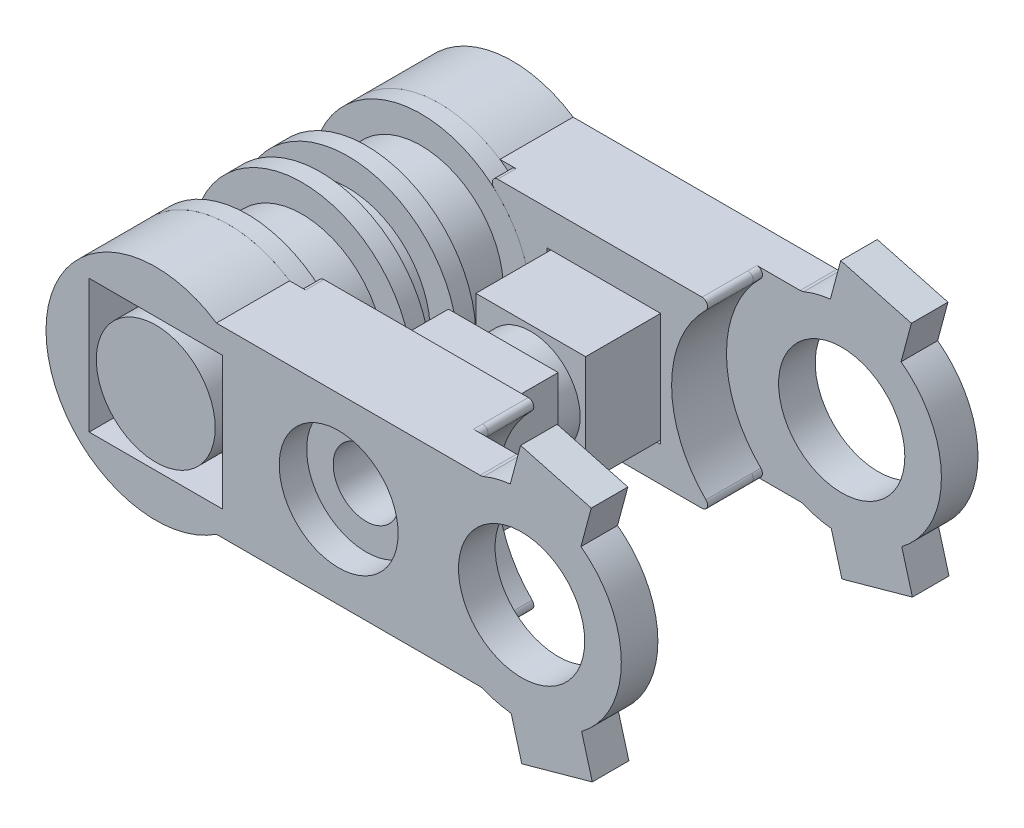
SolidWorks part; units mm, degrees
material "ABS"
ref_plane "正面" through (0, 0, 0) normal (0, 0, 1) x (1, 0, 0)
ref_plane "平面" through (0, 0, 0) normal (0, 1, 0) x (1, 0, 0)
ref_plane "右側面" through (0, 0, 0) normal (1, 0, 0) x (0, 0, -1)
sketch "ｽｹｯﾁ1" plane through (0, 0, 0) normal (0, 0, 1) x (1, 0, 0)
  circle A0 centre (0, 0) radius 4.5
  dimension "D1" = 9
extrude "ﾎﾞｽ - 押し出し1" add sketch "ｽｹｯﾁ1" along normal blind 3
sketch "ｽｹｯﾁ2" plane through (0, 0, 0) normal (0, 0, -1) x (-1, 0, 0)
  circle A0 centre (0, 0) radius 6
  dimension "D1" = 12
extrude "ﾎﾞｽ - 押し出し2" add sketch "ｽｹｯﾁ2" along normal blind 1
sketch "ｽｹｯﾁ3" plane through (0, 0, -1) normal (0, 0, -1) x (-1, 0, 0)
  circle A0 centre (0, 0) radius 4.5 construction
  circle A1 centre (0, 0) radius 4.5
extrude "ﾎﾞｽ - 押し出し3" add sketch "ｽｹｯﾁ3" along normal blind 1.5
sketch "ｽｹｯﾁ4" plane through (0, 0, -2.5) normal (0, 0, -1) x (-1, 0, 0)
  circle A1 centre (0, 0) radius 6
  circle A2 centre (0, 0) radius 6
  dimension "D1" = 0
extrude "ﾎﾞｽ - 押し出し4" add sketch "ｽｹｯﾁ4" along normal blind 1
sketch "ｽｹｯﾁ5" plane through (0, 0, -3.5) normal (0, 0, -1) x (-1, 0, 0)
  circle A0 centre (0, 0) radius 4.5 construction
  circle A1 centre (0, 0) radius 4.5
extrude "ﾎﾞｽ - 押し出し5" add sketch "ｽｹｯﾁ5" along normal blind 3
sketch "ｽｹｯﾁ6" plane through (0, 0, -6.5) normal (0, 0, -1) x (-1, 0, 0)
  circle A1 centre (0, 0) radius 6
  circle A2 centre (0, 0) radius 6
  dimension "D1" = 0
extrude "ﾎﾞｽ - 押し出し6" add sketch "ｽｹｯﾁ6" along normal blind 1
sketch "ｽｹｯﾁ7" plane through (0, 0, 3) normal (0, 0, 1) x (1, 0, 0)
  circle A1 centre (0, 0) radius 6
  circle A2 centre (0, 0) radius 6
  dimension "D1" = 0
extrude "ﾎﾞｽ - 押し出し7" add sketch "ｽｹｯﾁ7" along normal blind 1
sketch "ｽｹｯﾁ10" plane through (0, 0, 4) normal (0, 0, 1) x (1, 0, 0)
  line L1 (3.5, -3.5) -> (-3.5, -3.5)
  line L2 (3.5, -3.5) -> (3.5, 3.5)
  line L3 (3.5, 3.5) -> (-3.5, 3.5)
  line L4 (-3.5, -3.5) -> (-3.5, 3.5)
  line L5 (3.5, -3.5) -> (-3.5, 3.5) construction
  line L6 (3.5, 3.5) -> (-3.5, -3.5) construction
  point P0 (0, 0)
  dimension "D1" = 7
  dimension "D2" = 7
extrude "ﾎﾞｽ - 押し出し10" add sketch "ｽｹｯﾁ10" along normal blind 1.5
sketch "ｽｹｯﾁ11" plane through (0, 0, 5.5) normal (0, 0, 1) x (1, 0, 0)
  circle A0 centre (0, 0) radius 3.25
  dimension "D1" = 6.5
extrude "ﾎﾞｽ - 押し出し11" add sketch "ｽｹｯﾁ11" along normal blind 2.5
ref_plane "平面1" through (0, 0, -1.75) normal (0, 0, 1) x (1, 0, 0)
mirror "ﾐﾗｰ1" about plane through (0, 0, -1.75) normal (0, 0, 1) of "ﾎﾞｽ - 押し出し11", "ﾎﾞｽ - 押し出し10"
sketch "ｽｹｯﾁ12" plane through (0, 0, 4) normal (0, 0, 1) x (1, 0, 0)
  line L0 (0, 0) -> (20, 0) construction
  line L1 (3.3166, 5) -> (16.1672, 5)
  line L3 (16.1672, -5) -> (3.3166, -5)
  line L8 (3.64, -3.64) -> (3.64, 3.64)
  line L9 (-3.64, -3.64) -> (3.64, -3.64)
  line L10 (-3.64, 3.64) -> (-3.64, -3.64)
  line L11 (3.64, 3.64) -> (-3.64, 3.64)
  line L12 (3.64, -3.64) -> (3.64, 3.64)
  line L13 (-3.64, -3.64) -> (3.64, -3.64)
  line L14 (-3.64, 3.64) -> (-3.64, -3.64)
  line L15 (3.64, 3.64) -> (-3.64, 3.64)
  circle A0 centre (0, 0) radius 6 construction
  circle A1 centre (20, 0) radius 3.45 construction
  arc A2 (3.3166, 5) -> (3.3166, -5) centre (0, 0) ccw
  circle A3 centre (20, 0) radius 5.45 construction
  circle A4 centre (20, 0) radius 6.3 construction
  arc A5 (16.1672, 5) -> (16.1672, -5) centre (20, 0) ccw
  circle A6 centre (20, 0) radius 6 construction
  circle A7 centre (0, 0) radius 6 construction
  circle A8 centre (20, 0) radius 3.25 construction
  circle A9 centre (0, 0) radius 3.25 construction
  dimension "D3" = 20
  dimension "D6" = 0.3
  dimension "D2" = 5
  dimension "D7" = 5
  dimension "D4" = 0.2
  dimension "D5" = 2
  dimension "D1" = 0.14
extrude "ﾎﾞｽ - 押し出し12" add sketch "ｽｹｯﾁ12" along normal blind 1.5 separate body
sketch "ｽｹｯﾁ13" plane through (0, 0, 5.5) normal (0, 0, 1) x (1, 0, 0)
  line L6 (16.1672, 5) -> (3.3166, 5) construction
  line L9 (16.1672, 5) -> (3.3166, 5) construction
  line L10 (15.3664, 5) -> (3.7135, 5)
  line L11 (15.3664, -5) -> (3.7135, -5)
  circle A1 centre (0, 0) radius 3.25 construction
  arc A7 (16.1672, 5) -> (16.1672, -5) centre (20, 0) ccw construction
  arc A8 (15.577, 4.4864) -> (15.577, -4.4864) centre (20, 0) ccw
  circle A10 centre (0, 0) radius 5.69 construction
  circle A11 centre (0, 0) radius 3.39 construction
  circle A12 centre (0, 0) radius 5.39 construction
  arc A13 (3.5275, 4.4646) -> (3.5275, -4.4646) centre (0, 0) cw
  arc A14 (15.3664, -5) -> (15.577, -4.4864) centre (15.3664, -4.7) ccw
  arc A15 (15.577, 4.4864) -> (15.3664, 5) centre (15.3664, 4.7) ccw
  arc A16 (3.7135, 5) -> (3.5275, 4.4646) centre (3.7135, 4.7) ccw
  arc A17 (3.5275, -4.4646) -> (3.7135, -5) centre (3.7135, -4.7) ccw
  point P24 (2.7159, 5)
  point P29 (2.7159, -5)
  dimension "D1" = 0.14
  dimension "D3" = 0.3
  dimension "D4" = 2
  dimension "D2" = 0.3
extrude "ﾎﾞｽ - 押し出し13" add sketch "ｽｹｯﾁ13" along normal blind 0.5
fillet "ﾌｨﾚｯﾄ9" radius 0.3 2 edges at (16.1672, -5, 4.75) (16.1672, 5, 4.75)
sketch "ｽｹｯﾁ14" plane through (0, 0, 6) normal (0, 0, 1) x (1, 0, 0)
  line L0 (3.7135, 5) -> (17.7301, 5)
  line L3 (3.7135, -5) -> (17.7301, -5)
  arc A0 (17.7301, 5) -> (17.9208, 5.0378) centre (17.7301, 5.5) ccw
  arc A1 (17.7301, -5) -> (17.9208, -5.0378) centre (17.7301, -5.5) cw
  arc A4 (3.5275, -4.4646) -> (3.7135, -5) centre (3.7135, -4.7) ccw construction
  arc A7 (3.5275, -4.4646) -> (3.5275, 4.4646) centre (0, 0) ccw construction
  arc A8 (3.7135, 5) -> (3.5275, 4.4646) centre (3.7135, 4.7) ccw construction
  arc A9 (3.5275, -4.4646) -> (3.7135, -5) centre (3.7135, -4.7) ccw
  arc A10 (3.7135, 5) -> (3.5275, 4.4646) centre (3.7135, 4.7) ccw
  arc A11 (3.5275, -4.4646) -> (3.5275, 4.4646) centre (0, 0) ccw
  circle A12 centre (20, 0) radius 5.45 construction
  arc A13 (17.9208, 5.0378) -> (17.9208, -5.0378) centre (20, 0) cw
  circle A14 centre (20, 0) radius 3.45 construction
  circle A15 centre (20, 0) radius 3.45
  point P19 (17.8315, -5)
  point P22 (17.8315, 5)
  point P24 (17.8315, 5)
  point P27 (17.8315, -5)
  dimension "D1" = 0.5
extrude "ﾎﾞｽ - 押し出し14" add sketch "ｽｹｯﾁ14" along normal blind 2
sketch "ｽｹｯﾁ15" plane through (0, 0, 4) normal (0, 0, -1) x (-1, 0, 0)
  line L0 (-15.3664, 5) -> (-4.1952, 5)
  line L1 (-3.3166, 5) -> (-16.1672, 5) construction
  line L2 (-15.3664, -5) -> (-4.1952, -5)
  line L3 (-16.1672, -5) -> (-3.3166, -5) construction
  circle A2 centre (0, 0) radius 6 construction
  arc A3 (-3.9955, 4.4762) -> (-3.9955, -4.4762) centre (0, 0) ccw
  arc A7 (-4.1952, -5) -> (-3.9955, -4.4762) centre (-4.1952, -4.7) ccw
  arc A8 (-4.1952, 5) -> (-3.9955, 4.4762) centre (-4.1952, 4.7) cw
  arc A10 (-15.577, -4.4864) -> (-15.3664, -5) centre (-15.3664, -4.7) ccw construction
  arc A11 (-15.577, -4.4864) -> (-15.577, 4.4864) centre (-20, 0) ccw construction
  arc A12 (-15.3664, 5) -> (-15.577, 4.4864) centre (-15.3664, 4.7) ccw construction
  arc A13 (-15.577, -4.4864) -> (-15.3664, -5) centre (-15.3664, -4.7) ccw
  arc A14 (-15.577, -4.4864) -> (-15.577, 4.4864) centre (-20, 0) ccw
  arc A15 (-15.3664, 5) -> (-15.577, 4.4864) centre (-15.3664, 4.7) ccw
  point P26 (-3.3166, -5)
  point P29 (-3.3166, 5)
  dimension "D2" = 0.3
extrude "ﾎﾞｽ - 押し出し15" add sketch "ｽｹｯﾁ15" along normal blind 1
mirror "ﾐﾗｰ2" about plane through (0, 0, -1.75) normal (0, 0, 1) of bodies 116
sketch "ｽｹｯﾁ16" plane through (0, 0, 8) normal (0, 0, 1) x (1, 0, 0)
  line L0 (0, 0) -> (20, 0) construction
  circle A0 centre (20, 0) radius 3.45 construction
  circle A1 centre (10, 0) radius 1.8
  dimension "D1" = 3.6
extrude "ｶｯﾄ - 押し出し1" cut sketch "ｽｹｯﾁ16" against normal through all
sketch "ｽｹｯﾁ17" plane through (0, 0, -6.5) normal (0, 0, 1) x (1, 0, 0)
  line L1 (13.1, -3.1) -> (6.9, -3.1)
  line L2 (13.1, -3.1) -> (13.1, 3.1)
  line L3 (13.1, 3.1) -> (6.9, 3.1)
  line L4 (6.9, -3.1) -> (6.9, 3.1)
  line L5 (13.1, -3.1) -> (6.9, 3.1) construction
  line L6 (13.1, 3.1) -> (6.9, -3.1) construction
  point P0 (10, 0)
  dimension "D2" = 6.2
  dimension "D1" = 6.2
extrude "ｶｯﾄ - 押し出し2" cut sketch "ｽｹｯﾁ17" against normal blind 2
sketch "ｽｹｯﾁ18" plane through (0, 0, 3) normal (0, 0, -1) x (-1, 0, 0)
  line L0 (-7, 3) -> (-13, 3)
  line L5 (-13, 3) -> (-13, -3)
  line L6 (-13, -3) -> (-7, -3)
  line L7 (-7, -3) -> (-7, 3)
  line L8 (-13.1, -3.1) -> (-6.9, -3.1)
  line L9 (-6.9, -3.1) -> (-6.9, 3.1)
  line L10 (-6.9, 3.1) -> (-13.1, 3.1)
  line L11 (-13.1, 3.1) -> (-13.1, -3.1)
  line L12 (-13.1, -3.1) -> (-6.9, -3.1) construction
  line L13 (-6.9, -3.1) -> (-6.9, 3.1) construction
  line L14 (-6.9, 3.1) -> (-13.1, 3.1) construction
  line L15 (-13.1, 3.1) -> (-13.1, -3.1) construction
  dimension "D1" = 0
  dimension "D2" = 0.1
extrude "ﾎﾞｽ - 押し出し16" add sketch "ｽｹｯﾁ18" along normal up to surface (11.5 mm away) up to face at (10, 0, -8.5)
sketch "ｽｹｯﾁ19" plane through (0, 0, 3) normal (0, 0, 1) x (1, 0, 0)
  circle A0 centre (10, 0) radius 1.8 construction
  circle A1 centre (10, 0) radius 1.8
extrude "ｶｯﾄ - 押し出し3" cut sketch "ｽｹｯﾁ19" against normal through all
sketch "ｽｹｯﾁ20" plane through (0, 0, -1.75) normal (0, 0, 1) x (1, 0, 0)
  line L4 (13, 3) -> (7, 3)
  line L5 (13, -3) -> (13, 3)
  line L6 (7, -3) -> (13, -3)
  line L7 (7, 3) -> (7, -3)
  line L8 (13, 3) -> (7, 3)
  line L9 (13, -3) -> (13, 3)
  line L10 (7, -3) -> (13, -3)
  line L11 (7, 3) -> (7, -3)
  circle A1 centre (10, 0) radius 2.7
  dimension "D2" = 5.4
  dimension "D1" = 0
extrude "ｶｯﾄ - 押し出し4" cut sketch "ｽｹｯﾁ20" against normal blind 0.75 and the other way blind 0.75
sketch "ｽｹｯﾁ21" plane through (0, 0, 8) normal (0, 0, 1) x (1, 0, 0)
  circle A0 centre (10, 0) radius 3.25
  dimension "D1" = 6.5
extrude "ｶｯﾄ - 押し出し5" cut sketch "ｽｹｯﾁ21" against normal blind 1.5
sketch "ｽｹｯﾁ22" plane through (0, 0, -11.5) normal (0, 0, -1) x (-1, 0, 0)
  line L1 (-11.6743, 2.9) -> (-13.3486, 0)
  line L2 (-13.3486, 0) -> (-11.6743, -2.9)
  line L3 (-11.6743, -2.9) -> (-8.3257, -2.9)
  line L4 (-8.3257, -2.9) -> (-6.6514, 0)
  line L5 (-6.6514, 0) -> (-8.3257, 2.9)
  line L6 (-8.3257, 2.9) -> (-11.6743, 2.9)
  circle A0 centre (-10, 0) radius 2.9 construction
  dimension "D1" = 5.8
extrude "ｶｯﾄ - 押し出し6" cut sketch "ｽｹｯﾁ22" against normal blind 1
sketch "ｽｹｯﾁ23" plane through (0, 0, 8) normal (0, 0, 1) x (1, 0, 0)
  line L0 (20, 0) -> (21.4106, 5.2643) construction
  line L1 (19.0128, 4.0433) -> (22.8765, 3.008)
  line L2 (19.0128, 4.0433) -> (19.9446, 7.5206)
  line L3 (19.9446, 7.5206) -> (23.8083, 6.4853)
  line L4 (22.8765, 3.008) -> (23.8083, 6.4853)
  line L5 (19.0128, 4.0433) -> (23.8083, 6.4853) construction
  line L6 (19.9446, 7.5206) -> (22.8765, 3.008) construction
  line L7 (20, 0) -> (20, 5.45) construction
  line L8 (20, -5.45) -> (20, 0) construction
  line L9 (20, 0) -> (21.4564, -5.2518) construction
  line L10 (20.0102, -7.5208) -> (19.0482, -4.0517)
  line L11 (20.0102, -7.5208) -> (23.8647, -6.4518)
  line L12 (19.0482, -4.0517) -> (22.9027, -2.9828)
  line L13 (23.8647, -6.4518) -> (22.9027, -2.9828)
  line L14 (20.0102, -7.5208) -> (22.9027, -2.9828) construction
  line L15 (19.0482, -4.0517) -> (23.8647, -6.4518) construction
  arc A0 (17.9208, -5.0378) -> (17.9208, 5.0378) centre (20, 0) ccw construction
  point P0 (21.4106, 5.2643)
  dimension "D1" = 1.8
  dimension "D2" = 4
  dimension "D3" = 15
  dimension "D4" = 15.5
extrude "ﾎﾞｽ - 押し出し17" add sketch "ｽｹｯﾁ23" against normal up to surface (2 mm away) up to face at (17.3986, 0, 6)
sketch "ｽｹｯﾁ24" plane through (0, 0, -11.5) normal (0, 0, -1) x (-1, 0, 0)
  line L12 (-22.8765, 3.008) -> (-19.0128, 4.0433)
  line L13 (-23.8083, 6.4853) -> (-22.8765, 3.008)
  line L14 (-19.9446, 7.5206) -> (-23.8083, 6.4853)
  line L15 (-19.0128, 4.0433) -> (-19.9446, 7.5206)
  line L16 (-22.8765, 3.008) -> (-19.0128, 4.0433)
  line L17 (-23.8083, 6.4853) -> (-22.8765, 3.008)
  line L18 (-19.9446, 7.5206) -> (-23.8083, 6.4853)
  line L19 (-19.0128, 4.0433) -> (-19.9446, 7.5206)
  line L20 (-20.0102, -7.5208) -> (-19.0482, -4.0517)
  line L21 (-19.0482, -4.0517) -> (-22.9027, -2.9828)
  line L22 (-22.9027, -2.9828) -> (-23.8647, -6.4518)
  line L23 (-23.8647, -6.4518) -> (-20.0102, -7.5208)
  line L24 (-20.0102, -7.5208) -> (-19.0482, -4.0517)
  line L25 (-19.0482, -4.0517) -> (-22.9027, -2.9828)
  line L26 (-22.9027, -2.9828) -> (-23.8647, -6.4518)
  line L27 (-23.8647, -6.4518) -> (-20.0102, -7.5208)
  dimension "D1" = 0
  dimension "D2" = 0
extrude "ﾎﾞｽ - 押し出し18" add sketch "ｽｹｯﾁ24" against normal up to surface (2 mm away) up to face at (17.3986, 0, -9.5)
sketch "ｽｹｯﾁ25" plane through (0, 0, -9) normal (0, 0, -1) x (-1, 0, 0)
  line L0 (3.64, 3.64) -> (3.64, -3.64) construction
  line L1 (-3.64, -3.64) -> (-3.64, 3.64) construction
  line L2 (-3.7135, -5) -> (-3.3166, -5)
  line L3 (-3.3166, 5) -> (-3.7135, 5)
  line L4 (-3.7135, -5) -> (-3.3166, -5)
  line L5 (-3.3166, 5) -> (-3.7135, 5)
  line L6 (-3.64, 3.64) -> (3.64, 3.64) construction
  line L7 (3.64, 3.64) -> (3.64, -3.64)
  line L8 (-3.64, -3.64) -> (-3.64, 3.64)
  line L9 (-3.64, 3.64) -> (3.64, 3.64)
  line L12 (-3.64, -3.64) -> (3.64, -3.64)
  line L13 (3.64, -3.64) -> (-3.64, -3.64) construction
  arc A4 (-3.7135, -5) -> (-3.5275, -4.4646) centre (-3.7135, -4.7) ccw
  arc A5 (-3.3166, -5) -> (-3.3166, 5) centre (0, 0) ccw
  arc A6 (-3.5275, 4.4646) -> (-3.7135, 5) centre (-3.7135, 4.7) ccw
  arc A7 (-3.5275, 4.4646) -> (-3.5275, -4.4646) centre (0, 0) ccw
  arc A8 (-3.7135, -5) -> (-3.5275, -4.4646) centre (-3.7135, -4.7) ccw
  arc A9 (-3.3166, -5) -> (-3.3166, 5) centre (0, 0) ccw
  arc A10 (-3.5275, 4.4646) -> (-3.7135, 5) centre (-3.7135, 4.7) ccw
  arc A11 (-3.5275, 4.4646) -> (-3.5275, -4.4646) centre (0, 0) ccw
  dimension "D1" = 0
extrude "ﾎﾞｽ - 押し出し19" add sketch "ｽｹｯﾁ25" along normal up to surface (2.5 mm away) up to face at (16.4182, 0.0039, -11.5)
sketch "ｽｹｯﾁ26" plane through (0, 0, 5.5) normal (0, 0, 1) x (1, 0, 0)
  line L2 (3.3166, -5) -> (3.7135, -5)
  line L3 (3.7135, 5) -> (3.3166, 5)
  line L4 (-3.64, 3.64) -> (-3.64, -3.64)
  line L5 (-3.64, -3.64) -> (3.64, -3.64)
  line L6 (3.64, -3.64) -> (3.64, 3.64)
  line L7 (3.64, 3.64) -> (-3.64, 3.64)
  line L8 (-3.64, 3.64) -> (-3.64, -3.64)
  line L9 (-3.64, -3.64) -> (3.64, -3.64)
  line L10 (3.64, -3.64) -> (3.64, 3.64)
  line L11 (3.64, 3.64) -> (-3.64, 3.64)
  line L12 (3.3166, -5) -> (3.7135, -5)
  line L13 (3.7135, 5) -> (3.3166, 5)
  arc A4 (3.3166, 5) -> (3.3166, -5) centre (0, 0) ccw
  arc A5 (3.7135, 5) -> (3.5275, 4.4646) centre (3.7135, 4.7) ccw
  arc A6 (3.5275, -4.4646) -> (3.5275, 4.4646) centre (0, 0) ccw
  arc A7 (3.5275, -4.4646) -> (3.7135, -5) centre (3.7135, -4.7) ccw
  arc A8 (3.3166, 5) -> (3.3166, -5) centre (0, 0) ccw
  arc A9 (3.7135, 5) -> (3.5275, 4.4646) centre (3.7135, 4.7) ccw
  arc A10 (3.5275, -4.4646) -> (3.5275, 4.4646) centre (0, 0) ccw
  arc A11 (3.5275, -4.4646) -> (3.7135, -5) centre (3.7135, -4.7) ccw
  dimension "D1" = 0
  dimension "D2" = 0
extrude "ﾎﾞｽ - 押し出し20" add sketch "ｽｹｯﾁ26" along normal up to surface (2.5 mm away) up to face at (16.4182, 0.0039, 8)
equation "\"D7@ｽｹｯﾁ12\"=\"D2@ｽｹｯﾁ12\""
equation "\"D1@ｽｹｯﾁ17\"=\"D2@ｽｹｯﾁ17\""
